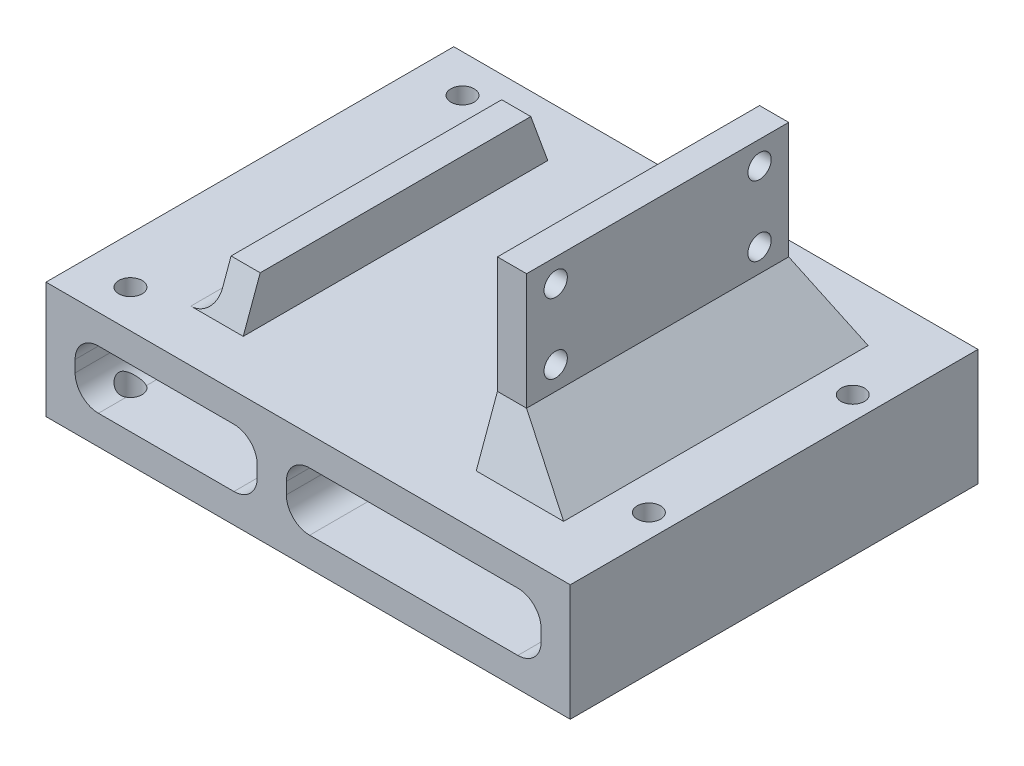
SolidWorks part; units mm, degrees
ref_plane "Ön Düzlem" through (0, 0, 0) normal (0, 0, 1) x (1, 0, 0)
ref_plane "Üst Düzlem" through (0, 0, 0) normal (0, 1, 0) x (1, 0, 0)
ref_plane "Sağ Düzlem" through (0, 0, 0) normal (1, 0, 0) x (0, 0, -1)
sketch "Çizim1" plane through (0, 0, 0) normal (0, 0, 1) x (1, 0, 0)
  line L0 (-50.0557, 3.3365) -> (-45.0557, 3.3365)
  line L1 (-45.0557, 3.3365) -> (-45.0557, -4.6635)
  line L2 (-45.0557, -4.6635) -> (-5.0557, -4.6635)
  line L3 (-5.0557, -4.6635) -> (-5.0557, 25.3365)
  line L4 (-5.0557, 25.3365) -> (-0.0557, 25.3365)
  line L5 (-0.0557, 25.3365) -> (-0.0557, 5.3365)
  line L6 (9.9443, -4.6635) -> (19.9443, -4.6635)
  line L7 (19.9443, -4.6635) -> (19.9443, -24.6635)
  line L8 (19.9443, -24.6635) -> (-70.0557, -24.6635)
  line L9 (-70.0557, -24.6635) -> (-70.0557, -4.6635)
  line L10 (-70.0557, -4.6635) -> (-54.0557, -4.6635)
  line L11 (-50.0557, -0.6635) -> (-50.0557, 3.3365)
  line L12 (-0.0557, 5.3365) -> (9.9443, -4.6635)
  arc A0 (-54.0557, -4.6635) -> (-50.0557, -0.6635) centre (-54.0557, -0.6635) ccw
  point P7 (-0.0557, -4.6635)
  point P14 (-50.0557, -4.6635)
  dimension "D10" = 4
  dimension "D1" = 40
  dimension "D2" = 30
  dimension "D3" = 8
  dimension "D4" = 20
  dimension "D5" = 20
  dimension "D6" = 5
  dimension "D7" = 5
  dimension "D8" = 20
  dimension "D9" = 20
extrude "Yükseklik-Ekstrüzyon1" add sketch "Çizim1" along normal blind 45
sketch "Çizim2" plane through (0, 0, 45) normal (0, 0, 1) x (1, 0, 0)
  line L0 (-70.0557, -4.6635) -> (-70.0557, -24.6635) construction
  line L1 (-61.0557, -9.6635) -> (-37.7964, -9.6635)
  line L2 (-65.0557, -13.6635) -> (-65.0557, -15.6635)
  line L3 (-61.0557, -19.6635) -> (-37.7964, -19.6635)
  line L4 (-33.7964, -13.6635) -> (-33.7964, -15.6635)
  line L5 (10.9443, -9.6635) -> (-24.7964, -9.6635)
  line L6 (14.9443, -13.6635) -> (14.9443, -15.6635)
  line L7 (10.9443, -19.6635) -> (-24.7964, -19.6635)
  line L8 (-28.7964, -13.6635) -> (-28.7964, -15.6635)
  line L9 (-54.0557, -4.6635) -> (-70.0557, -4.6635) construction
  line L10 (-70.0557, -24.6635) -> (19.9443, -24.6635) construction
  line L11 (-5.0557, -4.6635) -> (-45.0557, -4.6635) construction
  line L12 (19.9443, -24.6635) -> (19.9443, -4.6635) construction
  arc A0 (10.9443, -19.6635) -> (14.9443, -15.6635) centre (10.9443, -15.6635) ccw
  arc A1 (14.9443, -13.6635) -> (10.9443, -9.6635) centre (10.9443, -13.6635) ccw
  arc A2 (-28.7964, -15.6635) -> (-24.7964, -19.6635) centre (-24.7964, -15.6635) ccw
  arc A3 (-28.7964, -13.6635) -> (-24.7964, -9.6635) centre (-24.7964, -13.6635) cw
  arc A4 (-33.7964, -13.6635) -> (-37.7964, -9.6635) centre (-37.7964, -13.6635) ccw
  arc A5 (-33.7964, -15.6635) -> (-37.7964, -19.6635) centre (-37.7964, -15.6635) cw
  arc A6 (-65.0557, -15.6635) -> (-61.0557, -19.6635) centre (-61.0557, -15.6635) ccw
  arc A7 (-65.0557, -13.6635) -> (-61.0557, -9.6635) centre (-61.0557, -13.6635) cw
  dimension "D8" = 4
  dimension "D1" = 5
  dimension "D2" = 5
  dimension "D3" = 5
  dimension "D4" = 5
  dimension "D5" = 5
  dimension "D6" = 5
  dimension "D7" = 5
sketch "Çizim3" plane through (0, -4.6635, 0) normal (0, 1, 0) x (1, 0, 0)
  line L0 (19.9443, -45) -> (9.9443, -45) construction
  line L1 (19.9443, 0) -> (9.9443, 0) construction
  line L2 (-54.0557, -45) -> (-70.0557, -45) construction
  line L4 (-54.0557, 0) -> (-70.0557, 0) construction
  circle A0 centre (15.9443, -40) radius 2
  circle A1 centre (15.9443, -5) radius 2
  circle A2 centre (-62.0557, -51) radius 2
  circle A3 centre (-62.0557, 6) radius 2
  dimension "D1" = 4
  dimension "D2" = 4
  dimension "D3" = 4
  dimension "D4" = 4
  dimension "D5" = 5
  dimension "D6" = 5
  dimension "D7" = 6
  dimension "D9" = 6
sketch "Çizim4" plane through (-0.0557, 0, 0) normal (1, 0, 0) x (0, 0, -1)
  line L0 (-45, 5.3365) -> (-45, 25.3365) construction
  line L1 (-45, 25.3365) -> (0, 25.3365) construction
  line L2 (-45, 5.3365) -> (0, 5.3365) construction
  line L3 (0, 5.3365) -> (0, 25.3365) construction
  circle A0 centre (-40, 21.3365) radius 2
  circle A1 centre (-5, 21.3365) radius 2
  circle A2 centre (-40, 9.3365) radius 2
  circle A3 centre (-5, 9.3365) radius 2
  dimension "D1" = 4
  dimension "D2" = 4
  dimension "D3" = 4
  dimension "D10" = 4
  dimension "D4" = 5
  dimension "D5" = 5
  dimension "D6" = 4
  dimension "D7" = 4
  dimension "D8" = 4
  dimension "D9" = 5
extrude "Kes-Ekstrüzyon3" cut sketch "Çizim4" against normal blind 45
sketch "Çizim5" plane through (0, 0, 45) normal (0, 0, 1) x (1, 0, 0)
  line L1 (-70.0557, -4.6635) -> (19.9443, -4.6635)
  line L2 (-70.0557, -4.6635) -> (-70.0557, -24.6635)
  line L3 (-70.0557, -24.6635) -> (19.9443, -24.6635)
  line L4 (19.9443, -4.6635) -> (19.9443, -24.6635)
extrude "Yükseklik-Ekstrüzyon2" add sketch "Çizim5" along normal blind 12.5
sketch "Çizim6" plane through (0, 0, 0) normal (0, 0, -1) x (-1, 0, 0)
  line L1 (-19.9443, -4.6635) -> (70.0557, -4.6635)
  line L2 (-19.9443, -4.6635) -> (-19.9443, -24.6635)
  line L3 (-19.9443, -24.6635) -> (70.0557, -24.6635)
  line L4 (70.0557, -4.6635) -> (70.0557, -24.6635)
extrude "Yükseklik-Ekstrüzyon3" add sketch "Çizim6" along normal blind 12.5
extrude "Kes-Ekstrüzyon4" cut sketch "Çizim2" against normal blind 97.5 and the other way blind 66
chamfer "Pah1" distance 10 angle 20 4 edges at (-49.5557, -4.6635, 0) (2.4443, -4.6635, 0) (2.4443, -4.6635, 45) (-49.5557, -4.6635, 45) first distance on face at (-48.69, -0.8292, 0) first distance on face at (-0.0557, 9.3365, 0) first distance on face at (-0.0557, 9.3365, 45) first distance on face at (-48.69, -0.8292, 45)
extrude "Kes-Ekstrüzyon5" cut sketch "Çizim3" against normal blind 52
